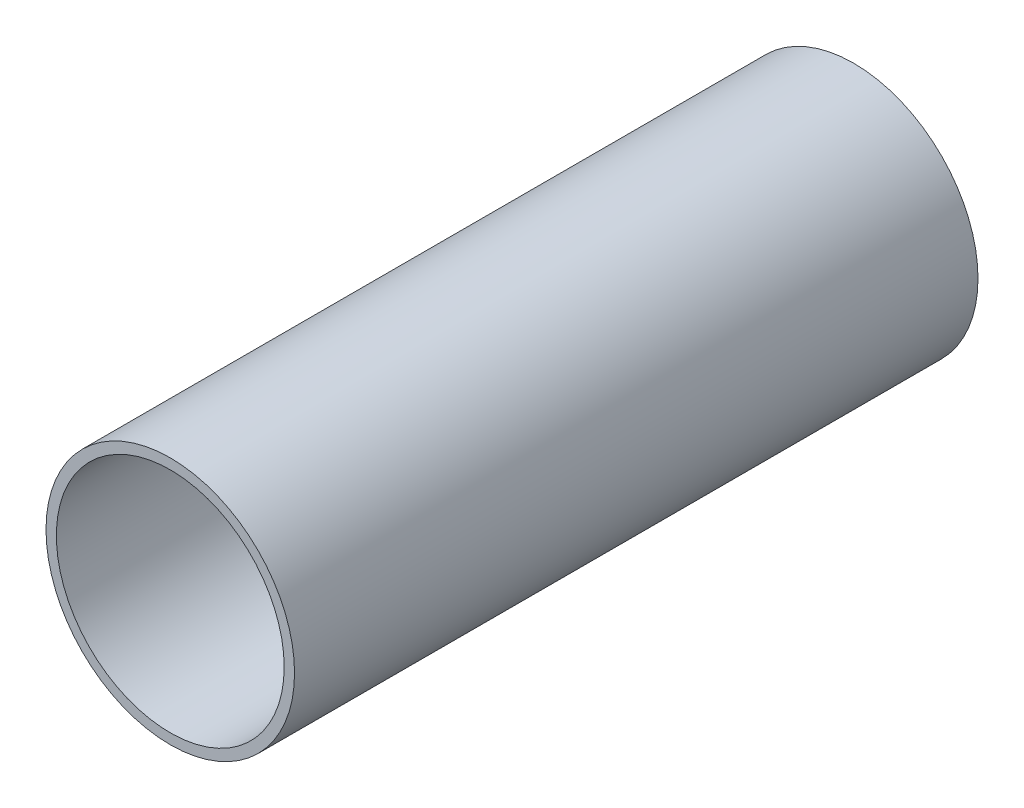
SolidWorks part; units mm, degrees
ref_plane "Front Plane" through (0, 0, 0) normal (0, 0, 1) x (1, 0, 0)
ref_plane "Top Plane" through (0, 0, 0) normal (0, 1, 0) x (1, 0, 0)
ref_plane "Right Plane" through (0, 0, 0) normal (1, 0, 0) x (0, 0, -1)
sketch "Sketch1" plane through (0, 0, 0) normal (0, 0, 1) x (1, 0, 0)
  circle A0 centre (0, 0) radius 63.5
  circle A1 centre (0, 0) radius 69.85
  circle A2 centre (0, 0) radius 76.2
  dimension "D1" = 152.4
  dimension "D2" = 139.7
  dimension "D3" = 127
extrude "Boss-Extrude1" add sketch "Sketch1" along normal blind 406.4 contours A2 A1 region at (-74.0447, 0, 0)
extrude "Boss-Extrude2" add sketch "Sketch1<3>" against normal blind 12.7 contours A1 A0 | A2 A1 region at (-67.8743, 0, 0) region at (-74.0447, 0, 0)
sketch "Sketch1<3>" plane through (0, 0, 0) normal (0, 0, 1) x (1, 0, 0) same geometry as "Sketch1"
